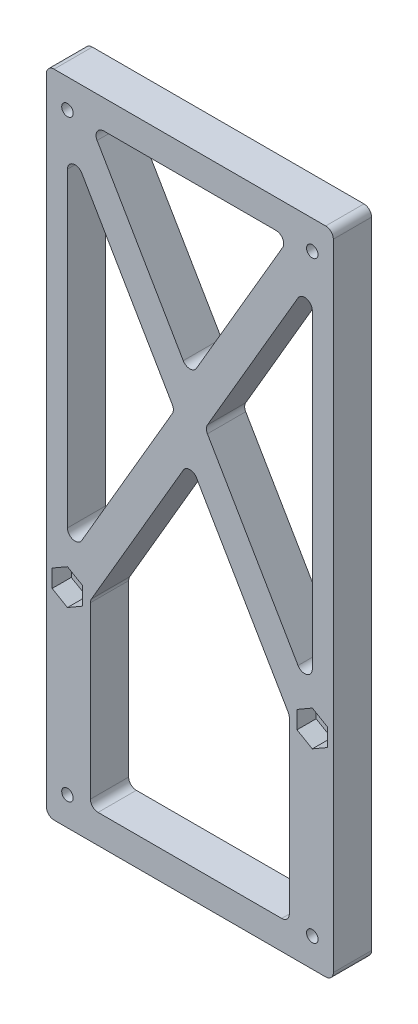
SolidWorks part; units mm, degrees
ref_plane "Front Plane" through (0, 0, 0) normal (1, 0, 0) x (0, 1, 0)
ref_plane "Top Plane" through (0, 0, 0) normal (0, 0, 1) x (0, 1, 0)
ref_plane "Right Plane" through (0, 0, 0) normal (0, 1, 0) x (-1, 0, 0)
sketch "Sketch1" plane through (0, 0, 0) normal (0, 0, 1) x (0, 1, 0)
  line L1 (-85, -37.5) -> (85, -37.5)
  line L2 (-85, -37.5) -> (-85, 37.5)
  line L3 (-85, 37.5) -> (85, 37.5)
  line L4 (85, -37.5) -> (85, 37.5)
  line L5 (-85, -37.5) -> (85, 37.5) construction
  line L6 (-85, 37.5) -> (85, -37.5) construction
  point P0 (0, 0)
  dimension "D1" = 170
  dimension "D2" = 75
extrude "Boss-Extrude1" add sketch "Sketch1" along normal blind 10
sketch "Sketch2" plane through (0, 0, 10) normal (0, 0, 1) x (1, 0, 0)
  line L0 (0, 85) -> (0, -85) construction
  line L1 (37.5, 85) -> (-37.5, 85) construction
  line L2 (-37.5, -85) -> (37.5, -85) construction
  line L3 (-37.5, 0) -> (37.5, 0) construction
  line L4 (-37.5, 85) -> (-37.5, -85) construction
  line L5 (37.5, -85) -> (37.5, 85) construction
  line L6 (-32, 85) -> (-32, -85) construction
  circle A0 centre (-32, 77.5) radius 1.5
  circle A1 centre (-32, -30.5) radius 1.5
  circle A2 centre (-32, -77.5) radius 1.5
  circle A3 centre (32, -77.5) radius 1.5
  circle A4 centre (32, -30.5) radius 1.5
  circle A5 centre (32, 77.5) radius 1.5
  point P20 (0, 0)
  dimension "D2" = 3
  dimension "D1" = 32
  dimension "D3" = 155
  dimension "D4" = 108
extrude "Cut-Extrude1" cut sketch "Sketch2" against normal through all
sketch "Sketch4" plane through (0, 0, 10) normal (0, 0, 1) x (1, 0, 0)
  line L0 (0, 85) -> (0, -85) construction
  line L1 (37.5, 85) -> (-37.5, 85) construction
  line L2 (-37.5, -85) -> (37.5, -85) construction
  line L3 (-32, -77.5) -> (-32, -30.5) construction
  line L4 (-32, -30.5) -> (-32, 77.5) construction
  line L5 (-32, 77.5) -> (32, 77.5) construction
  line L6 (-32, -24.5) -> (-32, 71.5)
  line L7 (-32, 71.5) -> (-4, 23.5)
  line L8 (-4, 23.5) -> (-32, -24.5)
  line L9 (-26, 77.5) -> (26, 77.5)
  line L10 (26, 77.5) -> (0, 32.9286)
  line L11 (0, 32.9286) -> (-26, 77.5)
  line L12 (-32, 23.5) -> (0, 23.5) construction
  line L13 (32, 71.5) -> (4, 23.5)
  line L14 (32, -24.5) -> (32, 71.5)
  line L15 (4, 23.5) -> (32, -24.5)
  line L16 (26, -30.5) -> (0, 14.0714)
  line L17 (0, 14.0714) -> (-26, -30.5)
  line L18 (-26, -30.5) -> (-26, -77.5)
  line L19 (-26, -77.5) -> (26, -77.5)
  line L20 (26, -77.5) -> (26, -30.5)
  line L21 (-32, -77.5) -> (32, -77.5) construction
  dimension "D1" = 6
  dimension "D2" = 6
  dimension "D3" = 4
extrude "Cut-Extrude2" cut sketch "Sketch4" against normal through all
fillet "Fillet1" radius 2 18 edges at (-26, -77.5, 5) (26, -77.5, 5) (26, -30.5, 5) (-26, -30.5, 5) (0, 14.0714, 5) (4, 23.5, 5) (-4, 23.5, 5) (0, 32.9286, 5) (32, 71.5, 5) (26, 77.5, 5) (-32, 71.5, 5) (-26, 77.5, 5) (-32, -24.5, 5) (32, -24.5, 5) (-37.5, -85, 5) (37.5, -85, 5) (-37.5, 85, 5) (37.5, 85, 5)
sketch "Sketch5" plane through (0, 0, 10) normal (0, 0, 1) x (1, 0, 0)
  line L0 (-32, -35.1188) -> (-32, -30.5) construction
  line L1 (-28, -32.8094) -> (-28, -28.1906)
  line L2 (-28, -28.1906) -> (-32, -25.8812)
  line L3 (-32, -25.8812) -> (-36, -28.1906)
  line L4 (-36, -28.1906) -> (-36, -32.8094)
  line L5 (-36, -32.8094) -> (-32, -35.1188)
  line L6 (-32, -35.1188) -> (-28, -32.8094)
  line L7 (0, -85) -> (0, 85) construction
  line L8 (-35.5, -85) -> (35.5, -85) construction
  line L9 (35.5, 85) -> (-35.5, 85) construction
  line L10 (32, -35.1188) -> (28, -32.8094)
  line L11 (36, -32.8094) -> (32, -35.1188)
  line L12 (36, -28.1906) -> (36, -32.8094)
  line L13 (32, -25.8812) -> (36, -28.1906)
  line L14 (28, -28.1906) -> (32, -25.8812)
  line L15 (28, -32.8094) -> (28, -28.1906)
  circle A0 centre (-32, -30.5) radius 4 construction
  dimension "D1" = 8
extrude "Cut-Extrude3" cut sketch "Sketch5" against normal blind 5
